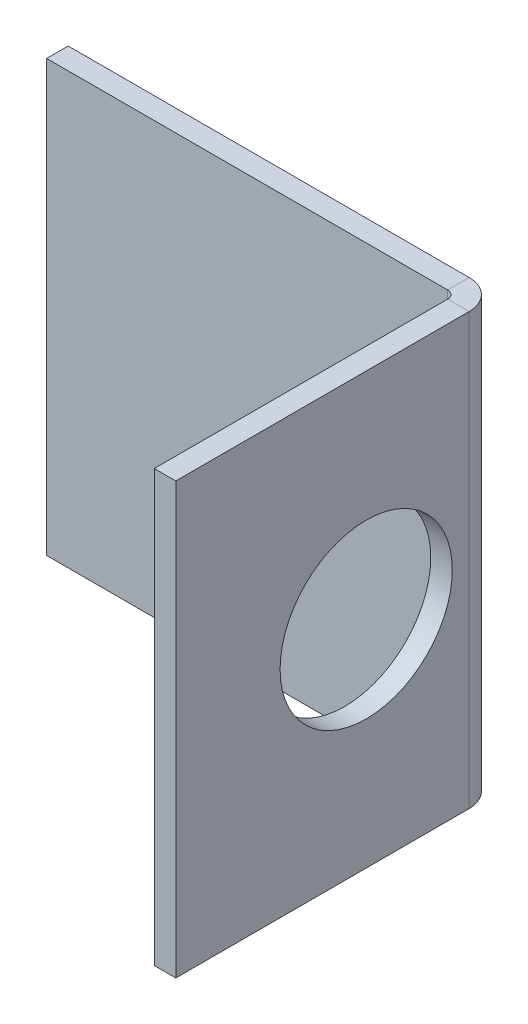
SolidWorks part; units mm, degrees
note: The reader was unsure of these and kept them because the rebuilt part matched: flange length of "Brida de arista1".
ref_plane "Alzado" through (0, 0, 0) normal (0, 0, 1) x (1, 0, 0)
ref_plane "Planta" through (0, 0, 0) normal (0, 1, 0) x (1, 0, 0)
ref_plane "Vista lateral" through (0, 0, 0) normal (1, 0, 0) x (0, 0, -1)
sketch "Croquis1" plane through (0, 0, 0) normal (0, 0, 1) x (1, 0, 0)
  line L0 (-32.962, 0) -> (32.962, 0) construction
  line L2 (-20, -20) -> (20, -20)
  line L3 (-20, -20) -> (-20, 20)
  line L4 (-20, 20) -> (20, 20)
  line L5 (20, -20) -> (20, 20)
  line L6 (-20, -20) -> (20, 20) construction
  line L7 (-20, 20) -> (20, -20) construction
  point P0 (0, 0)
  point P4 (0, 0)
  dimension "D1" = 40
  dimension "D2" = 40
base flange "Brida base1" sketch "Croquis1" thickness 2 reverse thickness direction yes parameters "D1"=0.7366
edge flange "Brida de arista1" sketch "Croquis10" flange angle 90 flange length 30 bend radius 0.7366 thickness 2 relief rectangular parameters "D6"=10
sketch "Croquis10" plane through (20, 0, 2) normal (1, 0, 0) x (0, 1, 0)
  line L0 (-20, 0) -> (20, 0) construction
  line L1 (-20, 0) -> (20, 0)
  line L2 (-20, 0) -> (-20, 28)
  line L3 (-20, 28) -> (20, 28)
  line L4 (20, 28) -> (20, 0)
bend "Pliegue de arista1" bend radius 0.7366 bend angle 90 parameters "D5"=1
sketch "Croquis11" plane through (18, 0, 0) normal (-1, 0, 0) x (0, 0, 1)
  circle A0 centre (12.31, 0) radius 8
  dimension "D1" = 16
extrude "Cortar-Extruir2" cut sketch "Croquis11" against normal up to next normal cut yes
sketch "Líneas de pliegue1" [suppressed] plane through (0, 0, 0) normal (0, 1, 0) x (1, 0, 0)
sketch "Cuadro delimitador1" [suppressed] plane through (0, 0, 0) normal (0, 1, 0) x (1, 0, 0)
sheet metal parameters "Chapa metálica1" thickness 2 parameters "D1"=0.7366
flat pattern "Chapa desplegada1" [suppressed]
sketch "Líneas de pliegue2" plane through (0, 0, 0) normal (0, 1, 0) x (1, 0, 0)
sketch3d "Cuadro delimitador2" [suppressed]
  line L0 (20, 30.5, 0) -> (20, -30.5, 0) construction
  line L1 (-20, 30.5, 0) -> (-20, -30.5, 0) construction
  line L2 (20, 30.5, 0) -> (-20, 30.5, 0) construction
  line L3 (20, -30.5, 0) -> (-20, -30.5, 0) construction
sheet metal parameters "Chapa metálica2" thickness 2 parameters "D1"=0.7366
flat pattern "Chapa desplegada1" [suppressed]
sketch "Líneas de pliegue2" plane through (0, 0, 0) normal (0, 0, -1) x (-1, 0, 0)
  line L0 (-18.6273, 30.5) -> (-18.6273, -30.5) construction
  line L1 (-18.6273, 30.5) -> (-18.6273, -30.5) construction
sketch3d "Cuadro delimitador2" [suppressed]
  line L0 (20, -30.5, 0) -> (-57.2546, -30.5, 0) construction
  line L1 (20, 30.5, 0) -> (-57.2546, 30.5, 0) construction
  line L2 (20, -30.5, 0) -> (20, 30.5, 0) construction
  line L3 (-57.2546, -30.5, 0) -> (-57.2546, 30.5, 0) construction
bend of the flat pattern "Aplanar-<Pliegue de arista1>1"
sketch "Croquis11-1" [suppressed] plane through (17.2546, 0, 2) normal (0, 0, 1) x (1, 0, 0)
  circle A0 centre (14.31, 0) radius 4.7578
sheet metal parameters "Chapa metálica4" thickness 2 parameters "D1"=0.7366
flat pattern "Chapa desplegada1" [suppressed]
sketch "Líneas de pliegue2" plane through (0, 0, 0) normal (0, 0, -1) x (-1, 0, 0)
  line L0 (-18.6273, 20) -> (-18.6273, -20) construction
  line L1 (-18.6273, 20) -> (-18.6273, -20) construction
sketch3d "Cuadro delimitador2" [suppressed]
  line L0 (20, -20, 0) -> (-47.2546, -20, 0) construction
  line L1 (20, 20, 0) -> (-47.2546, 20, 0) construction
  line L2 (20, -20, 0) -> (20, 20, 0) construction
  line L3 (-47.2546, -20, 0) -> (-47.2546, 20, 0) construction
bend of the flat pattern "Aplanar-<Pliegue de arista1>1"
sketch "Croquis11-1" plane through (17.2546, 0, 2) normal (0, 0, 1) x (1, 0, 0)
  circle A0 centre (12.31, 0) radius 8
  dimension "D1" = 16
